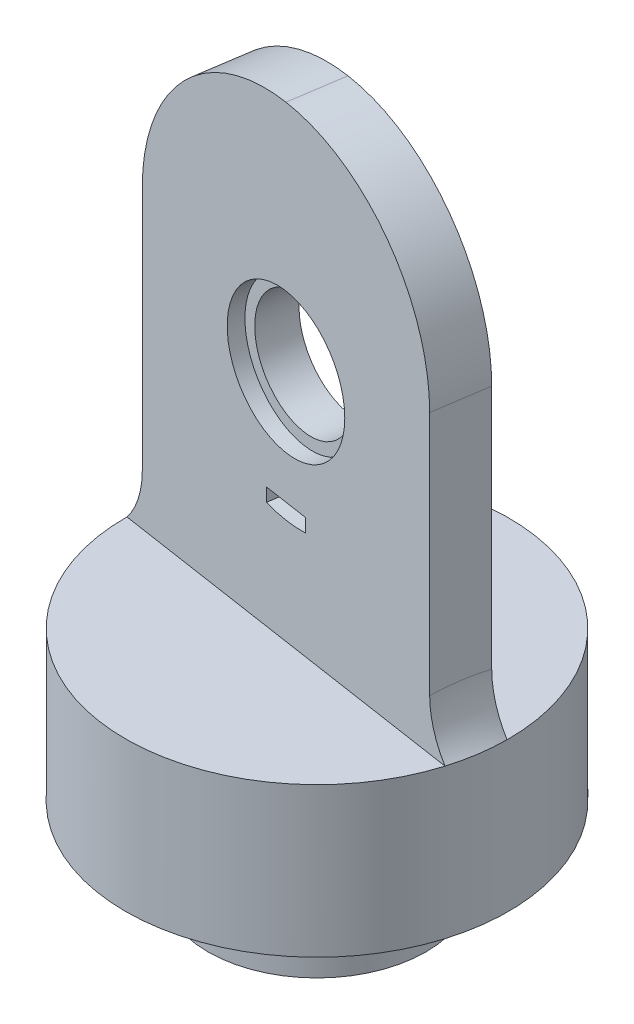
SolidWorks part; units mm, degrees
other "Markup1"
sketch "Sketch10" plane through (12.3, 18, -12.3) normal (0.8998, 0.4272, -0.0887) x (0.1084, -0.4159, -0.9029)
other "Markup2"
sketch "Sketch13" plane through (12.3, 18, -12.3) normal (0.6234, 0.4585, -0.6334) x (0.1049, -0.8518, -0.5133)
ref_plane "Front Plane" through (0, 0, 0) normal (0, 0, 1) x (1, 0, 0)
ref_plane "Top Plane" through (0, 0, 0) normal (0, 1, 0) x (1, 0, 0)
ref_plane "Right Plane" through (0, 0, 0) normal (1, 0, 0) x (0, 0, -1)
sketch "Sketch2" plane through (0, 0, 0) normal (0, 1, 0) x (1, 0, 0)
  circle A0 centre (0, 0) radius 12.3
extrude "Boss-Extrude1" add sketch "Sketch2" against normal blind 7.6 and the other way blind 2
sketch "Sketch3" plane through (0, -7.6, 0) normal (0, -1, 0) x (1, 0, 0)
  circle A0 centre (0, 0) radius 7
extrude "Boss-Extrude2" add sketch "Sketch3" along normal blind 4.9
sketch "Sketch4" plane through (0, -12.5, 0) normal (0, -1, 0) x (-1, 0, 0)
  circle A0 centre (0, 0) radius 3.25
extrude "Cut-Extrude1" cut sketch "Sketch4" against normal blind 12.7 contours A0
sketch "Sketch6" plane through (0, 2, 0) normal (0, 1, 0) x (1, 0, 0)
  line L0 (-12.3, 0) -> (12.3, 0) construction
  line L1 (-10.614, 3.3772) -> (11.138, 0.0834)
  line L2 (-10.614, 3.3772) -> (-11.138, -0.0834)
  line L3 (11.138, 0.0834) -> (10.614, -3.3772)
  line L4 (-11.138, -0.0834) -> (10.614, -3.3772)
  line L5 (-10.614, 3.3772) -> (10.614, -3.3772) construction
  line L6 (11.138, 0.0834) -> (-11.138, -0.0834) construction
  circle A0 centre (0, 0) radius 12.3 construction
  point P6 (0, 0)
extrude "Boss-Extrude4" add sketch "Sketch6" along normal blind 30 contours L1 L2 L4 L3
fillet "Fillet1" radius 11 2 edges at (-10.876, 32, -1.6469) (10.876, 32, 1.6469)
sketch "Sketch7" plane through (-0.262, 0, 1.7303) normal (-0.1497, 0, 0.9887) x (0.9887, 0, 0.1497)
  line L0 (0, 32) -> (0, 2) construction
  line L1 (-11, 2) -> (11, 2) construction
  circle A1 centre (0, 17) radius 4.5
extrude "Cut-Extrude2" cut sketch "Sketch7" against normal blind 1
sketch "Sketch9" plane through (-0.1123, 0, 0.7415) normal (-0.1497, 0, 0.9887) x (0.9887, 0, 0.1497)
  line L0 (0, 21.5) -> (0, 12.5) construction
  circle A0 centre (0, 17) radius 4.5 construction
  circle A1 centre (0, 17) radius 3.75
extrude "Cut-Extrude3" cut sketch "Sketch9" against normal up to next
sketch "Sketch17" plane through (-0.262, 0, 1.7303) normal (-0.1497, 0, 0.9887) x (0.9887, 0, 0.1497)
  line L0 (0, 12.5) -> (0, 21.5)
  circle A0 centre (0, 17) radius 4.5 construction
sketch "Sketch18" plane through (-0.262, 0, 1.7303) normal (-0.1497, 0, 0.9887) x (0.9887, 0, 0.1497)
  line L0 (0, 12.5) -> (0, 21.5) construction
  line L1 (0, 8.75) -> (0, 9.75)
  line L2 (0, 9.75) -> (1.5, 9.75)
  line L3 (1.5, 9.75) -> (1.5, 8.8875)
  line L4 (0, 9.75) -> (-1.5, 9.75)
  line L5 (-1.5, 9.75) -> (-1.5, 8.8875)
  circle A0 centre (0, 17) radius 8.25
extrude "Cut-Extrude4" cut sketch "Sketch18" against normal blind 2.5 contours L5 A0 L1 L4 | L1 A0 L3 L2 region at (-0.9858, 9.272, 1.6207) region at (0.4618, 9.272, 1.8399)
fillet "Fillet2" radius 5 2 edges at (10.876, 2, 1.6469) (-10.876, 2, -1.6469)
